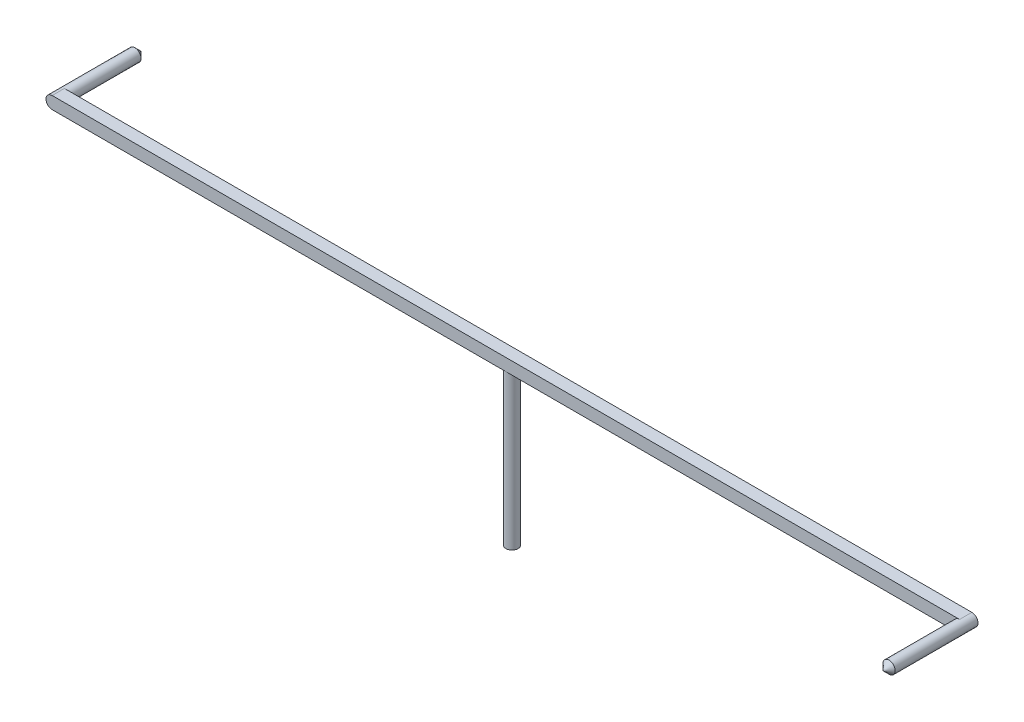
SolidWorks part; units mm, degrees
ref_plane "前视基准面" through (0, 0, 0) normal (0, 0, 1) x (1, 0, 0)
ref_plane "上视基准面" through (0, 0, 0) normal (0, 1, 0) x (1, 0, 0)
ref_plane "右视基准面" through (0, 0, 0) normal (1, 0, 0) x (0, 0, -1)
sketch "草图1" plane through (0, 0, 0) normal (0, 1, 0) x (1, 0, 0)
  circle A0 centre (0, 0) radius 0.4
  dimension "D1" = 0.8
extrude "凸台-拉伸1" add sketch "草图1" along normal blind 10
sketch "草图2" plane through (0, 10, 0) normal (0, 1, 0) x (1, 0, 0)
  line L1 (-30, 0.4) -> (30, 0.4)
  line L2 (-30, 0.4) -> (-30, -0.4)
  line L3 (-30, -0.4) -> (30, -0.4)
  line L4 (30, 0.4) -> (30, -0.4)
  circle A0 centre (0, 0) radius 0.4 construction
  dimension "D1" = 30
  dimension "D2" = 30
extrude "凸台-拉伸2" add sketch "草图2" along normal blind 0.8
fillet "圆角1" radius 0.4 4 edges at (30, 10, 0) (30, 10.8, 0) (-30, 10, 0) (-30, 10.8, 0)
sketch "草图3" plane through (0, 0, 0.4) normal (0, 0, 1) x (1, 0, 0)
  circle A0 centre (29.6, 10.4) radius 0.4
  dimension "D1" = 0.8
extrude "凸台-拉伸3" add sketch "草图3" along normal blind 5
sketch "草图4" plane through (0, 0, -0.4) normal (0, 0, -1) x (-1, 0, 0)
  circle A0 centre (29.6, 10.4) radius 0.4
  dimension "D1" = 0.8
extrude "凸台-拉伸4" add sketch "草图4" along normal blind 5
chamfer "倒角1" distance 0.4 angle 45 2 edges at (-30, 10.4, -5.4) (30, 10.4, 5.4)
